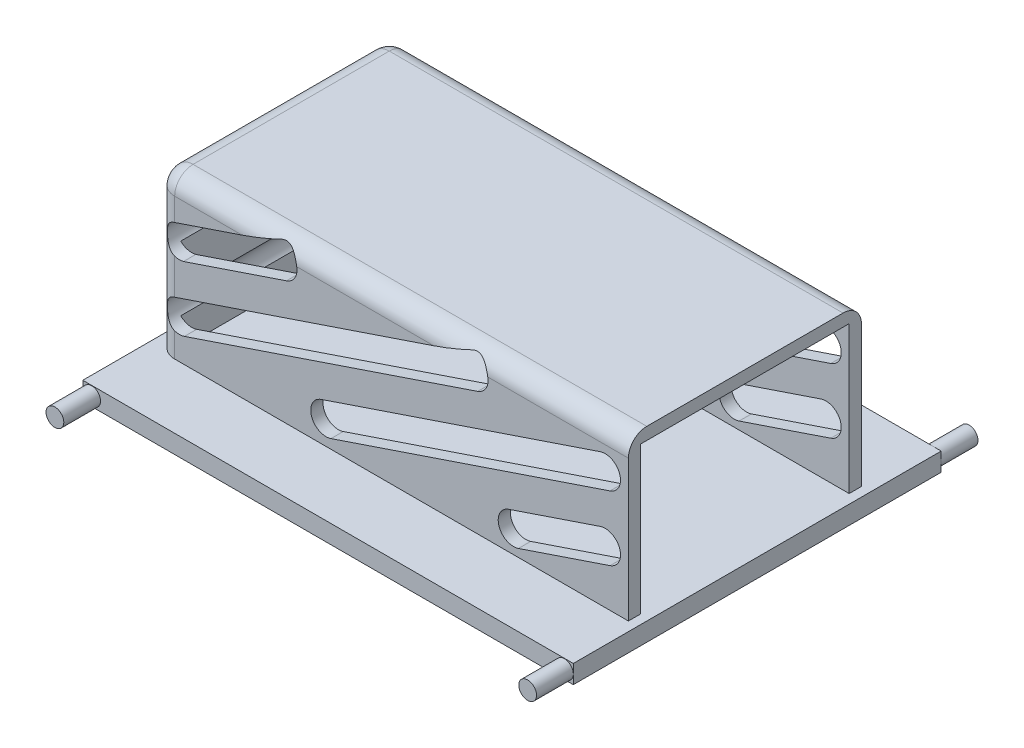
SolidWorks part; units mm, degrees
ref_plane "前视基准面" through (0, 0, 0) normal (0, 0, 1) x (1, 0, 0)
ref_plane "上视基准面" through (0, 0, 0) normal (0, 1, 0) x (1, 0, 0)
ref_plane "右视基准面" through (0, 0, 0) normal (1, 0, 0) x (0, 0, -1)
sketch "草图1" plane through (0, 0, 0) normal (0, 0, 1) x (1, 0, 0)
  line L14 (0, 1.5) -> (30, 1.5)
  line L15 (0, 1.5) -> (-40, 1.5)
  line L16 (-40, 1.5) -> (-40, -1.5)
  line L17 (-40, -1.5) -> (40, -1.5)
  line L18 (40, -1.5) -> (40, 1.5)
  line L21 (30, 1.5) -> (40, 1.5)
  dimension "D1" = 40
  dimension "D3" = 80
extrude "凸台-拉伸1" add sketch "草图1" along normal blind 55.815 and the other way blind 4.185
sketch "草图11" plane through (0, 1.5, 0) normal (0, 1, 0) x (1, 0, 0)
  line L0 (0, 7.8076) -> (0, -57.1665) construction
  line L1 (-53.1193, -26.3293) -> (53.0606, -26.3293) construction
  line L3 (36.5, -9.3293) -> (-36.5, -9.3293)
  line L6 (-36.5, -43.3292) -> (-36.5, -9.3293)
  line L17 (-36.5, -43.3292) -> (36.5, -43.3292)
  line L22 (-38.5, -9.3293) -> (-38.5, -7.3293)
  line L23 (-38.5, -7.3293) -> (36.5, -7.3293)
  line L24 (36.5, -7.3293) -> (38.5, -7.3293)
  line L25 (38.5, -7.3293) -> (38.5, -9.3293)
  line L26 (38.5, -9.3293) -> (36.5, -9.3293)
  line L28 (36.5, -43.3292) -> (38.5, -43.3292)
  line L29 (-38.5, -9.3293) -> (-38.5, -45.3292)
  line L30 (-38.5, -45.3292) -> (38.5, -45.3292)
  line L31 (38.5, -45.3292) -> (38.5, -43.3292)
  point P10 (0, -43.3292)
  point P11 (0, -9.3293)
  dimension "D3" = 2
  dimension "D1" = 2
  dimension "D2" = 36.5
  dimension "D4" = 2
  dimension "D6" = 2
extrude "凸台-拉伸4" add sketch "草图11" along normal blind 24
sketch "草图13" plane through (0, 0, 55.815) normal (0, 0, 1) x (1, 0, 0)
  line L0 (-40, 0) -> (-38.55, 0) construction
  line L1 (-40, 1.5) -> (-40, -1.5) construction
  line L2 (0, 3.1954) -> (0, -2.7808) construction
  line L3 (-38.55, 0) -> (38.55, 0) construction
  circle A0 centre (-38.55, 0) radius 1.45
  circle A1 centre (38.55, 0) radius 1.45
  dimension "D2" = 77.1
  dimension "D1" = 1.45
extrude "凸台-拉伸5" add sketch "草图13" along normal blind 6
sketch "草图14" plane through (0, 0, -4.185) normal (0, 0, -1) x (-1, 0, 0)
  line L0 (0, 3.5812) -> (0, -3.0035) construction
  line L1 (-40, 0) -> (-38.55, 0) construction
  line L2 (-40, -1.5) -> (-40, 1.5) construction
  circle A0 centre (-38.55, 0) radius 1.45
  circle A1 centre (38.55, 0) radius 1.45
  dimension "D1" = 1.45
extrude "凸台-拉伸6" add sketch "草图14" along normal blind 6
sketch "草图15" plane through (0, 25.5, 0) normal (0, 1, 0) x (1, 0, 0)
  line L0 (-38.5, -7.3293) -> (-38.5, -45.3292)
  line L1 (-38.5, -45.3292) -> (38.5, -45.3292)
  line L2 (38.5, -45.3292) -> (38.5, -7.3293)
  line L3 (38.5, -7.3293) -> (-38.5, -7.3293)
extrude "凸台-拉伸7" add sketch "草图15" along normal blind 2
sketch "草图16" plane through (0, 0, 45.3292) normal (0, 0, 1) x (1, 0, 0)
  line L0 (-38.5, 14.5) -> (0, 27.5) construction
  line L1 (-38.5, 27.5) -> (-38.5, 1.5) construction
  line L2 (-38.5, 27.5) -> (38.5, 27.5) construction
  line L3 (-19.25, 21) -> (-20.8496, 25.7372) construction
  line L6 (-19.25, 21) -> (-17.6504, 16.2628) construction
  line L7 (-17.6504, 16.2628) -> (-16.0508, 11.5255) construction
  line L8 (-16.0508, 11.5255) -> (-14.4512, 6.7883) construction
  line L9 (-14.4512, 6.7883) -> (-12.8517, 2.0511) construction
  line L15 (40, 1.5) -> (-40, 1.5) construction
  line L17 (38.5, 27.5) -> (38.5, 1.5) construction
  line L18 (-12.8517, 2.0511) -> (-11.2521, -2.6861) construction
  line L19 (-11.2521, -2.6861) -> (-9.6525, -7.4234) construction
  line L20 (-9.6525, -7.4234) -> (-8.0529, -12.1606) construction
  line L22 (-35.6577, 18.0984) -> (-34.7102, 18.4183)
  line L24 (-11.2521, -2.6861) -> (1.1453, 1.5) construction
  line L25 (-26.9257, 25.0344) -> (-24.6529, 18.3035) construction
  line L27 (-9.6525, -7.4234) -> (16.7744, 1.5) construction
  line L28 (16.7744, 1.5) -> (38.5, 8.8359) construction
  line L29 (-8.0529, -12.1606) -> (32.4035, 1.5) construction
  line L31 (-20.0498, 23.3686) -> (-38.5, 17.1387) construction
  line L32 (-38.5, 17.1387) -> (-35.6577, 18.0984)
  line L33 (-20.0498, 23.3686) -> (-8.0529, 27.5) construction
  line L34 (-16.8506, 13.8942) -> (-38.5, 6.584) construction
  line L35 (-16.8506, 13.8942) -> (23.4436, 27.5) construction
  line L37 (-13.6515, 4.4197) -> (38.5, 22.0293) construction
  line L39 (-18.7345, 26.4514) -> (-35.3624, 20.8368)
  line L40 (-10.4523, -5.0548) -> (38.5, 11.4746) construction
  line L41 (-17.2601, 21.6719) -> (-34.0581, 15.9999)
  line L42 (-35.6577, 7.5437) -> (-34.7102, 7.8636)
  line L43 (-35.6577, 7.5437) -> (-33.289, 8.3435)
  line L46 (-10.8879, 18.5462) -> (-9.1227, 13.3184) construction
  line L47 (-35.51, 10.2323) -> (12.313, 26.3803)
  line L48 (13.9126, 21.6431) -> (-33.9104, 5.495)
  line L49 (35.6577, 21.0695) -> (34.7102, 20.7496)
  line L50 (-11.6089, 7.7481) -> (33.9104, 23.1182)
  line L51 (35.51, 18.381) -> (-10.0093, 3.0108)
  line L52 (16.9221, 4.1885) -> (19.7644, 5.1483)
  line L53 (35.6577, 10.5148) -> (34.7102, 10.1949)
  line L54 (18.9646, 7.5169) -> (33.9104, 12.5635)
  line L55 (20.5642, 2.7797) -> (35.51, 7.8263)
  arc A4 (-10.0093, 3.0108) -> (-11.6089, 7.7481) centre (-10.8091, 5.3795) cw
  arc A10 (-34.0581, 15.9999) -> (-35.3624, 20.8368) centre (-34.7102, 18.4183) cw
  arc A11 (-18.7345, 26.4514) -> (-17.2601, 21.6719) centre (-18.0554, 24.0437) cw
  arc A12 (-33.9104, 5.495) -> (-35.51, 10.2323) centre (-34.7102, 7.8636) cw
  arc A13 (35.51, 18.381) -> (33.9104, 23.1182) centre (34.7102, 20.7496) ccw
  arc A14 (13.9126, 21.6431) -> (12.313, 26.3803) centre (13.1128, 24.0117) ccw
  arc A15 (18.9646, 7.5169) -> (20.5642, 2.7797) centre (19.7644, 5.1483) ccw
  arc A16 (33.9104, 12.5635) -> (35.51, 7.8263) centre (34.7102, 10.1949) cw
  dimension "D10" = 3
  dimension "D11" = 1
  dimension "D12" = 3
  dimension "D13" = 3
  dimension "D15" = 3
  dimension "D16" = 1
  dimension "D17" = 2.5
  dimension "D18" = 1
  dimension "D19" = 3
  dimension "D20" = 1
  dimension "D1" = 5
  dimension "D2" = 5
  dimension "D3" = 5
  dimension "D4" = 5
  dimension "D5" = 5
  dimension "D6" = 5
  dimension "D7" = 5
  dimension "D8" = 5
  dimension "D9" = 3
extrude "切除-拉伸2" cut sketch "草图16" against normal blind 38 contours A11 L39 A10 L41 | L48 A14 L47 A12 | L51 A13 L50 A4 | A16 L54 A15 L55 region at (-26.385, 21.2296, 45.3292) region at (-10.7987, 15.9377, 45.3292) region at (11.9505, 13.0645, 45.3292) region at (27.2373, 7.6716, 45.3292)
fillet "圆角2" radius 3 1 edges at (-38.5, 27.5, 26.3293)
fillet "圆角3" radius 3 3 edges at (-38.5, 13, 7.3293) (-37.6213, 26.6213, 7.3293) (1.5, 27.5, 7.3293)
fillet "圆角4" radius 3 3 edges at (-38.5, 13, 45.3292) (-37.6213, 26.6213, 45.3292) (1.5, 27.5, 45.3292)
